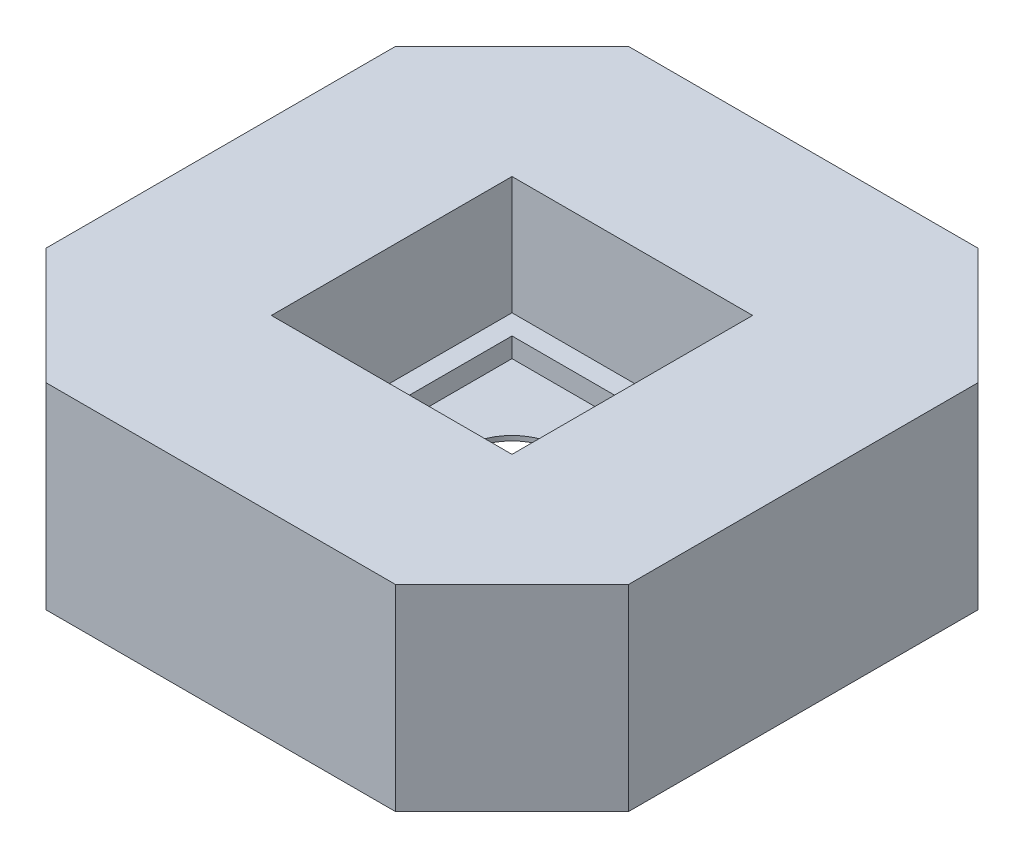
SolidWorks part; units mm, degrees
ref_plane "前视基准面" through (0, 0, 0) normal (0, 0, 1) x (1, 0, 0)
ref_plane "上视基准面" through (0, 0, 0) normal (0, 1, 0) x (1, 0, 0)
ref_plane "右视基准面" through (0, 0, 0) normal (1, 0, 0) x (0, 0, -1)
sketch "草图1" plane through (0, 0, 0) normal (0, 1, 0) x (1, 0, 0)
  line L0 (-305, 183) -> (-183, 305)
  line L1 (-183, -305) -> (183, -305)
  line L2 (-305, -183) -> (-305, 183)
  line L3 (-183, 305) -> (183, 305)
  line L4 (305, -183) -> (305, 183)
  line L5 (-305, -305) -> (305, 305) construction
  line L6 (-305, 305) -> (305, -305) construction
  line L7 (-305, -183) -> (-183, -305)
  line L8 (183, -305) -> (305, -183)
  line L9 (183, 305) -> (305, 183)
  point P0 (0, 0)
  dimension "D1" = 610
  dimension "D2" = 610
extrude "凸台-拉伸1" add sketch "草图1" along normal blind 206
sketch "草图3" plane through (0, 206, 0) normal (0, 1, 0) x (1, 0, 0)
  line L1 (126, 126) -> (-126, 126)
  line L2 (126, 126) -> (126, -126)
  line L3 (126, -126) -> (-126, -126)
  line L4 (-126, 126) -> (-126, -126)
  line L5 (126, 126) -> (-126, -126) construction
  line L6 (126, -126) -> (-126, 126) construction
  point P0 (0, 0)
  dimension "D1" = 252
  dimension "D2" = 252
extrude "切除-拉伸1" cut sketch "草图3" against normal blind 123.6 contours L2 L1 L4 L3
sketch "草图5" plane through (0, 82.4, 0) normal (0, 1, 0) x (1, 0, 0)
  line L1 (-105, 105) -> (105, 105)
  line L2 (-105, 105) -> (-105, -105)
  line L3 (-105, -105) -> (105, -105)
  line L4 (105, 105) -> (105, -105)
  line L5 (-105, 105) -> (105, -105) construction
  line L6 (-105, -105) -> (105, 105) construction
  point P0 (0, 0)
  dimension "D1" = 210
  dimension "D2" = 210
extrude "切除-拉伸5" cut sketch "草图5" against normal blind 20.6 contours L2 L1 L4 L3
shell "抽壳9" thickness 5 removed face at (0, 0, 0)
sketch "草图6" plane through (0, 61.8, 0) normal (0, 1, 0) x (1, 0, 0)
  circle A0 centre (0, 0) radius 50
extrude "切除-拉伸6" cut sketch "草图6" against normal through all
ref_plane "基准面1" through (0, 0, 91.5) normal (0, 0, 1) x (1, 0, 0)
sketch "草图7" plane through (0, 0, 91.5) normal (0, 0, 1) x (1, 0, 0)
  line L0 (-131, 82.4) -> (-300, 112.1993)
  line L1 (-131, 77.4) -> (-131, 201) construction
  line L2 (-300, 201) -> (-300, 0) construction
  line L3 (131, 77.4) -> (-131, 77.4) construction
  dimension "D1" = 80
  dimension "D2" = 5
rib "筋1" sketch "草图7" sketch "草图7" thickness 10 extrusion direction parallel to sketch draft on no parameters "D1"=10
mirror "镜向1" about plane through (0, 0, 0) normal (0, 0, 1) of "筋1"
pattern_circular "阵列(圆周)1" count 4 over 360 about axis through (0, 56.8, 0) along (0, -1, 0) of "镜向1", "筋1"
